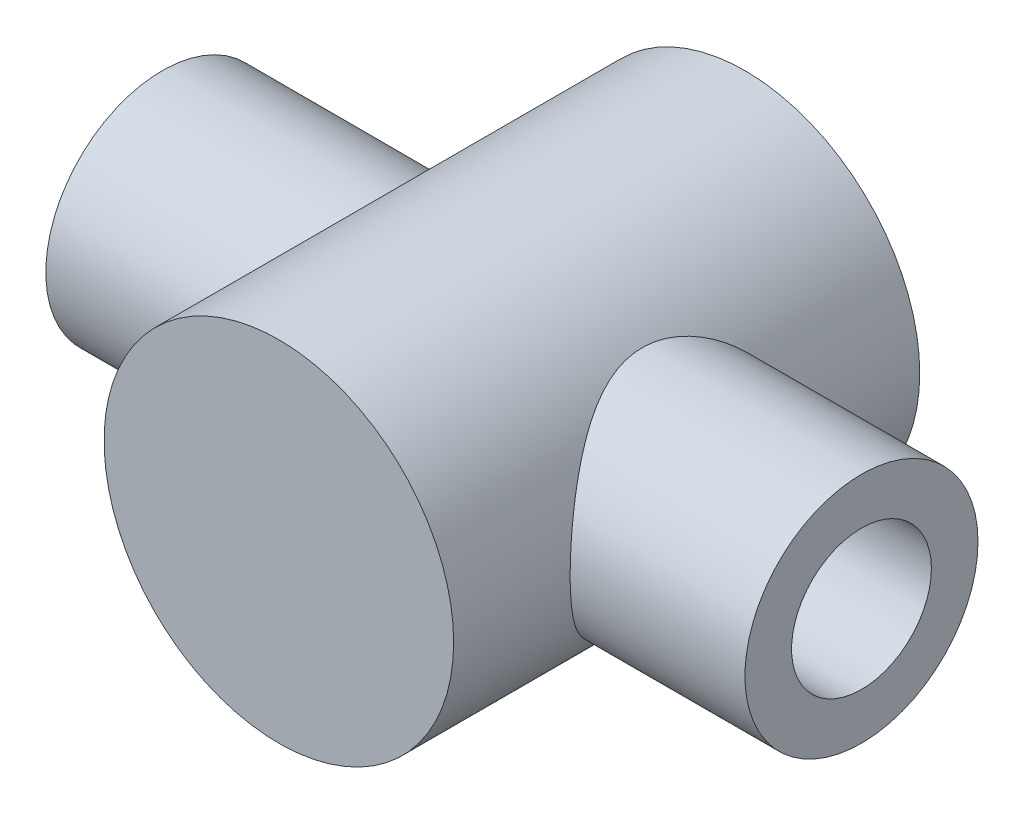
SolidWorks part; units mm, degrees
material "1023 Carbon Steel Sheet (SS)"
ref_plane "Front Plane" through (0, 0, 0) normal (0, 0, 1) x (1, 0, 0)
ref_plane "Top Plane" through (0, 0, 0) normal (0, 1, 0) x (1, 0, 0)
ref_plane "Right Plane" through (0, 0, 0) normal (1, 0, 0) x (0, 0, -1)
sketch "Sketch3" plane through (0, 0, 0) normal (0, 0, 1) x (1, 0, 0)
  circle A0 centre (0, 0) radius 15
extrude "Boss-Extrude2" add sketch "Sketch3" along normal blind 40
sketch "Sketch4" plane through (0, 0, 0) normal (1, 0, 0) x (0, 0, -1)
  circle A0 centre (-20, 0) radius 10
extrude "Boss-Extrude3" add sketch "Sketch4" along normal blind 30 and the other way blind 30
sketch "Sketch5" plane through (30, 0, 0) normal (1, 0, 0) x (0, 0, -1)
  circle A0 centre (-20, 0) radius 10 construction
  circle A1 centre (-20, 0) radius 10
  circle A2 centre (-20, 0) radius 6
extrude "Cut-Extrude2" cut sketch "Sketch5" against normal blind 10 flip side to cut
